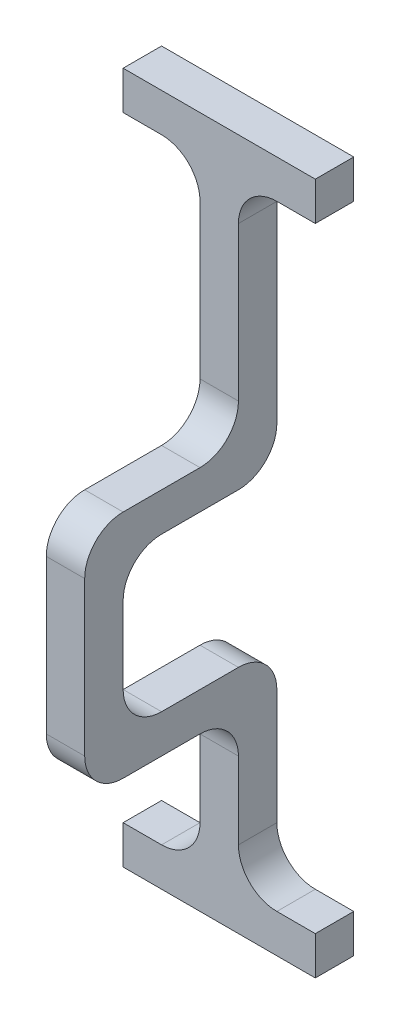
SolidWorks part; units mm, degrees
ref_plane "Front Plane" through (0, 0, 0) normal (0, 0, 1) x (1, 0, 0)
ref_plane "Top Plane" through (0, 0, 0) normal (0, 1, 0) x (1, 0, 0)
ref_plane "Right Plane" through (0, 0, 0) normal (1, 0, 0) x (0, 0, -1)
sketch "Sketch1" plane through (0, 0, 0) normal (1, 0, 0) x (0, 0, -1)
  line L0 (0, 0) -> (0, 80)
  line L1 (0, 80) -> (-10, 80)
  line L2 (-10, 80) -> (-10, 10)
  line L3 (-10, 10) -> (-50, 10)
  line L4 (-50, 10) -> (-50, -50)
  line L5 (-50, -50) -> (-10, -50)
  line L6 (-10, -50) -> (-10, -100)
  line L7 (-10, -100) -> (0, -100)
  line L8 (0, -100) -> (0, -40)
  line L9 (0, -40) -> (-40, -40)
  line L10 (-40, -40) -> (-40, 0)
  line L11 (-40, 0) -> (0, 0)
  dimension "D1" = 10
  dimension "D2" = 50
  dimension "D3" = 10
  dimension "D4" = 40
  dimension "D5" = 10
  dimension "D6" = 10
  dimension "D7" = 70
  dimension "D8" = 50
extrude "Boss-Extrude1" add sketch "Sketch1" along normal blind 10
sketch "Sketch2" plane through (10, 0, 0) normal (1, 0, 0) x (0, 0, -1)
  line L0 (0, 0) -> (0, 80) construction
  line L1 (-10, 80) -> (0, 80)
  line L2 (-10, 80) -> (-10, 70)
  line L3 (-10, 70) -> (0, 70)
  line L4 (0, 80) -> (0, 70)
  line L5 (0, -100) -> (0, -40) construction
  line L6 (-10, -100) -> (0, -100)
  line L7 (-10, -100) -> (-10, -90)
  line L8 (-10, -90) -> (0, -90)
  line L9 (0, -100) -> (0, -90)
extrude "Boss-Extrude2" add sketch "Sketch2" along normal blind 20
ref_plane "Plane1" through (5, 0, 0) normal (-1, 0, 0) x (0, 0, 1)
mirror "Mirror1" about plane through (5, 0, 0) normal (-1, 0, 0) of "Boss-Extrude2"
fillet "Fillet1" radius 10 12 edges at (10, -90, 5) (5, -40, 40) (0, -90, 5) (5, -40, 0) (5, 0, 0) (5, -50, 50) (5, 0, 40) (5, 10, 50) (5, -50, 10) (5, 10, 10)
ref_plane "Plane2" through (0, 0, 25) normal (0, 0, -1) x (-1, 0, 0)
ref_axis "Axis1" through (5, -31, 25) along (0, 1, 0)
